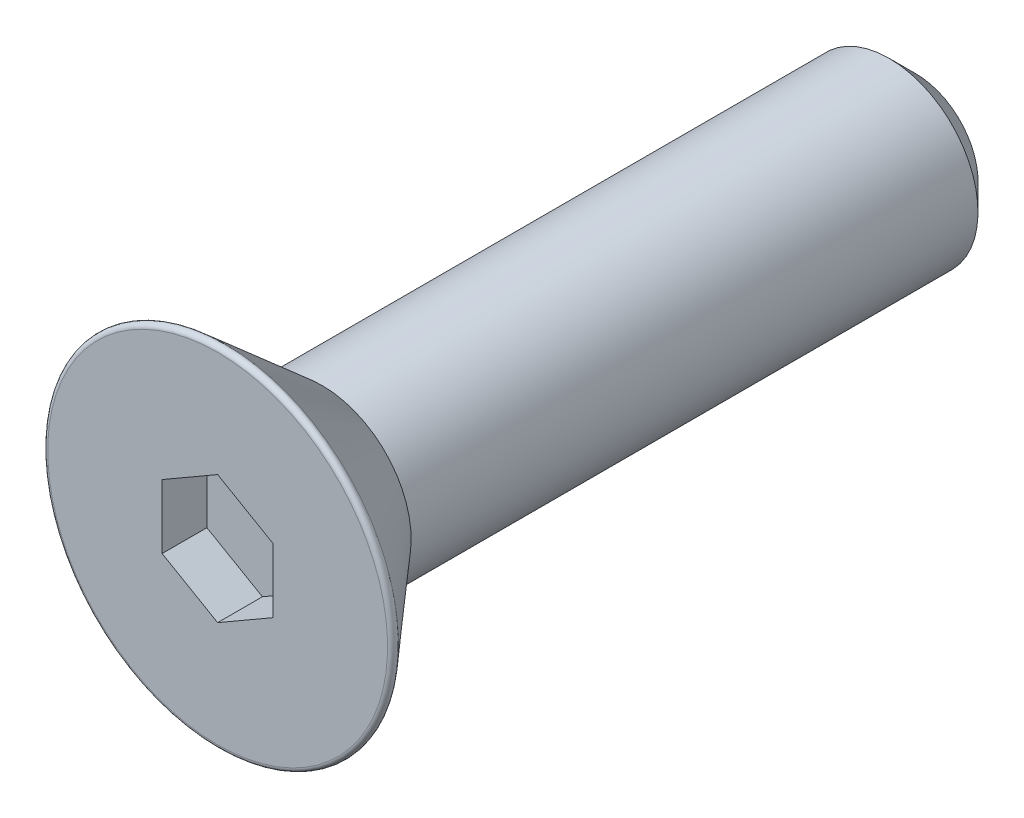
SolidWorks part; units mm, degrees
material "Alloy Steel"
ref_plane "Front Plane" through (0, 0, 0) normal (0, 0, 1) x (1, 0, 0)
ref_plane "Top Plane" through (0, 0, 0) normal (0, 1, 0) x (1, 0, 0)
ref_plane "Right Plane" through (0, 0, 0) normal (1, 0, 0) x (0, 0, -1)
sketch "Sketch1" plane through (0, 0, 0) normal (1, 0, 0) x (0, 0, -1)
  line L0 (-12.7, 0) -> (12.7, 0) construction
  line L1 (-12.7, 0) -> (-12.7, 6.7437)
  line L2 (-12.7, 6.7437) -> (-12.6182, 6.7437)
  line L3 (-12.6182, 6.7437) -> (-8.6106, 3.2599)
  line L4 (-12.6182, -6.7437) -> (-8.6106, -3.2599)
  line L5 (12.7, 0) -> (12.7, 3.175)
  line L6 (12.7, 3.175) -> (-8.6106, 3.175)
  line L7 (11.7475, 3.175) -> (12.7, 2.2225)
  line L8 (12.6206, 3.3125) -> (13.2556, 2.2126) construction
  line L9 (13.2556, 2.2126) -> (13.8906, 3.3125) construction
  line L10 (13.8906, 3.3125) -> (12.6206, 3.3125) construction
  line L11 (12.6603, 3.2437) -> (13.8509, 3.2437)
  line L12 (13.8509, 3.2437) -> (13.335, 2.3501)
  line L13 (13.335, 2.3501) -> (13.1762, 2.3501)
  line L14 (13.1762, 2.3501) -> (12.6603, 3.2437)
  line L15 (13.2556, 2.3501) -> (13.2556, 2.2126) construction
  line L16 (12.7, 3.175) -> (13.8112, 3.175) construction
  line L17 (13.2556, 3.3125) -> (13.2556, 3.175) construction
  line L18 (12.7, -3.175) -> (-8.6106, -3.175)
  arc A0 (-8.6106, 3.2599) -> (-8.3834, 3.175) centre (-8.3834, 3.5213) ccw
  point P2 (0, 0)
  point P23 (-10.6553, 0)
  point P27 (13.2556, 3.2437)
  point P30 (10.795, -3.175)
  point P31 (-8.6106, 6.7437)
  point P34 (-12.6182, -6.7437)
  dimension "Length" = 25.4
  dimension "Head Height" = 4.0894
  dimension "Head Diameter" = 13.4874
  dimension "Countersink Angle" = 82
  dimension "Screw Size Decimal Equivalent" = 6.35
  dimension "Pitch" = 1.27
  dimension "D4" = 0.1588
  dimension "D3" = 45
  dimension "D5" = 0.9525
  dimension "D6" = 2.0447
  dimension "D1" = 1.905
  dimension "D7" = 0.0818
sketch "Sketch8" plane through (0, 0, 0) normal (0, 0, 1) x (1, 0, 0)
  line L1 (0, 2.2914) -> (-1.9844, 1.1457)
  line L2 (-1.9844, 1.1457) -> (-1.9844, -1.1457)
  line L3 (-1.9844, -1.1457) -> (0, -2.2914)
  line L4 (0, -2.2914) -> (1.9844, -1.1457)
  line L5 (1.9844, -1.1457) -> (1.9844, 1.1457)
  line L6 (1.9844, 1.1457) -> (0, 2.2914)
  circle A0 centre (0, 0) radius 1.9844 construction
  dimension "Drive Size" = 3.9688
sketch "Sketch2" plane through (0, 0, 0) normal (1, 0, 0) x (0, 0, -1)
  line L0 (-12.6182, 6.7437) -> (-8.6106, 3.2599) construction
  line L1 (-12.7, 0) -> (-12.7, 6.7437) construction
  line L2 (-12.6182, 6.7437) -> (-8.5129, 3.175)
  line L3 (-12.7, 0) -> (-12.7, 6.7437)
  line L4 (-12.7, 6.7437) -> (-12.6182, 6.7437) construction
  line L5 (-12.7, 6.7437) -> (-12.6182, 6.7437)
  line L6 (-8.5129, 3.175) -> (11.7475, 3.175)
  line L7 (11.7475, 3.175) -> (12.7, 2.2225)
  line L8 (12.7, 2.2225) -> (12.7, 0)
  line L9 (12.7, 0) -> (-12.7, 0)
revolve "Revolve1" add sketch "Sketch2" angle 360 about L9
sketch "Sketch9" plane through (0, 0, 12.7) normal (0, 0, 1) x (1, 0, 0)
  line L0 (1.9844, -1.1457) -> (1.9844, 1.1457) construction
  line L1 (0, -2.2914) -> (1.9844, -1.1457) construction
  line L2 (-1.9844, -1.1457) -> (0, -2.2914) construction
  line L3 (-1.9844, 1.1457) -> (-1.9844, -1.1457) construction
  line L4 (0, 2.2914) -> (-1.9844, 1.1457) construction
  line L5 (1.9844, 1.1457) -> (0, 2.2914) construction
  line L6 (1.9844, -1.1457) -> (1.9844, 1.1457)
  line L7 (0, -2.2914) -> (1.9844, -1.1457)
  line L8 (-1.9844, -1.1457) -> (0, -2.2914)
  line L9 (-1.9844, 1.1457) -> (-1.9844, -1.1457)
  line L10 (0, 2.2914) -> (-1.9844, 1.1457)
  line L11 (1.9844, 1.1457) -> (0, 2.2914)
sketch "Sketch10" plane through (0, 0, 12.7) normal (0, 0, 1) x (1, 0, 0)
  circle A0 centre (0, 0) radius 2.2914
extrude "Cut-Extrude2" cut sketch "Sketch10" against normal up to vertex (2.0447 mm away) draft 45 up to point (0, 0, 10.6553)
extrude "Cut-Extrude1" cut sketch "Sketch9" against normal up to vertex (2.0447 mm away) up to point (0, 0, 10.6553)
ref_plane "Plane1" through (0, 0, 8.5129) normal (0, 0, 1) x (1, 0, 0)
split "Split1" trim tools "Plane1" bodies to split 111 resulting bodies 105 106
sketch "Sketch3" [suppressed] plane through (0, 0, -12.7) normal (0, 0, -1) x (-1, 0, 0)
  circle A0 centre (0, 0) radius 3.175 construction
  circle A1 centre (0, 0) radius 3.175
curve "Helix/Spiral1" [suppressed] pitch 1.27 height 25.4 turns 20
sketch "Sketch4" [suppressed] plane through (0, 0, 0) normal (1, 0, 0) x (0, 0, -1)
  line L0 (12.6603, 3.2437) -> (13.8509, 3.2437) construction
  line L1 (13.1762, 2.3501) -> (12.6603, 3.2437) construction
  line L2 (13.335, 2.3501) -> (13.1762, 2.3501) construction
  line L3 (13.8509, 3.2437) -> (13.335, 2.3501) construction
  line L4 (12.6603, 3.2437) -> (13.8509, 3.2437)
  line L5 (13.1762, 2.3501) -> (12.6603, 3.2437)
  line L6 (13.335, 2.3501) -> (13.1762, 2.3501)
  line L7 (13.8509, 3.2437) -> (13.335, 2.3501)
sweep "Cut-Sweep1" [suppressed] cut profiles "Sketch4" path "Helix/Spiral1"
sketch "Sketch7" plane through (0, 0, 8.5129) normal (0, 0, 1) x (1, 0, 0)
  circle A0 centre (0, 0) radius 3.175
extrude "Boss-Extrude2" add sketch "Sketch7" against normal up to next (21.2129 mm away) draft 20
sketch "Sketch12" plane through (0, 0, 0) normal (1, 0, 0) x (0, 0, -1)
  line L0 (-12.7, 0) -> (-12.7, 6.8148)
  line L1 (-12.7, 6.7437) -> (-12.7, -6.7437) construction
  line L2 (-12.7, 6.8148) -> (-11.9883, 6.1961)
  line L3 (-8.5129, 3.175) -> (-12.6182, 6.7437) construction
  line L4 (-12.0942, 6.2357) -> (-13.2564, 6.2357) construction
  line L5 (0, 0) -> (-12.2555, 0) construction
  line L6 (-12.2555, 6.0744) -> (-12.2555, 0)
  line L7 (-12.2555, 0) -> (-12.7, 0)
  arc A0 (-11.9883, 6.1961) -> (-12.2555, 6.0744) centre (-12.0942, 6.0744) ccw
  point P0 (-12.5595, 5.1424)
  point P15 (-12.6499, 6.4868)
  point P17 (-12.7, 6.3807)
  point P18 (-12.7, 6.2415)
  dimension "D1" = 6.2357
  dimension "D2" = 0.4445
revolve "Cut-Revolve1" cut sketch "Sketch12" angle 360 about L5
equation "\"D4@Sketch1\" = \"Pitch@Sketch1\" / 8"
equation "\"D5@Sketch1\"=\"Pitch@Sketch1\"*0.75"
equation "\"D4@Helix/Spiral1\"=\"Pitch@Sketch1\""
equation "\"D3@Helix/Spiral1\"=\"Length@Sketch1\""
equation "\"D6@Sketch1\"=\"Head Height@Sketch1\"/2"
equation "\"D1@Sketch1\"=\"Pitch@Sketch1\"*1.5"
equation "\"D7@Sketch1\"=\"Head Height@Sketch1\"*0.02"
equation "\"D1@Sketch12\"=0.4910in/2"
